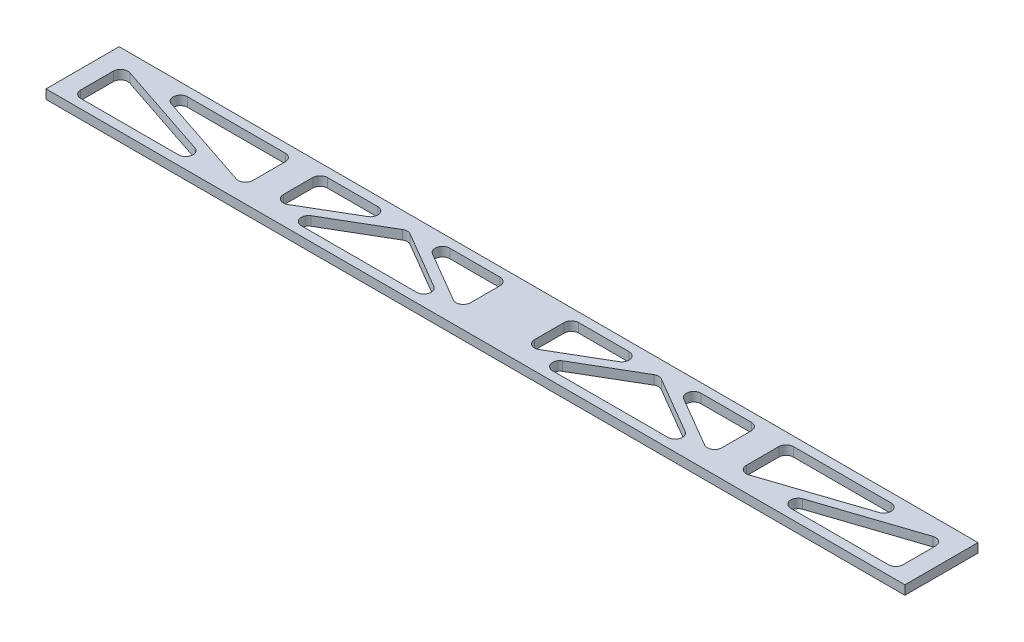
SolidWorks part; units mm, degrees
material "Plywood"
ref_plane "Front Plane" through (0, 0, 0) normal (0, 0, 1) x (1, 0, 0)
ref_plane "Top Plane" through (0, 0, 0) normal (0, 1, 0) x (1, 0, 0)
ref_plane "Right Plane" through (0, 0, 0) normal (1, 0, 0) x (0, 0, -1)
sketch "Sketch1" plane through (0, 0, 0) normal (0, 1, 0) x (1, 0, 0)
  line L1 (149.225, -12.7) -> (-149.225, -12.7)
  line L2 (149.225, -12.7) -> (149.225, 12.7)
  line L3 (149.225, 12.7) -> (-149.225, 12.7)
  line L4 (-149.225, -12.7) -> (-149.225, 12.7)
  point P0 (0, 12.7)
  point P6 (-149.225, 0)
  dimension "D1" = 25.4
  dimension "D2" = 298.45
extrude "Boss-Extrude1" add sketch "Sketch1" along normal blind 3.175
sketch "Sketch2" plane through (0, 3.175, 0) normal (0, 1, 0) x (1, 0, 0)
  line L0 (149.225, -12.7) -> (149.225, 12.7) construction
  line L2 (-149.225, 12.7) -> (-149.225, -12.7) construction
  line L4 (149.225, -12.7) -> (149.225, 12.7)
  line L6 (-149.225, 12.7) -> (-149.225, -12.7)
  line L8 (149.225, 9.525) -> (-149.225, 9.525)
  line L9 (-149.225, -9.525) -> (149.225, -9.525)
  line L10 (-142.875, 9.525) -> (-142.875, -9.525)
  line L11 (-80.9625, 9.525) -> (-80.9625, -9.525) construction
  line L12 (142.875, 9.525) -> (142.875, -9.525)
  line L13 (0, -9.525) -> (0, 9.525) construction
  line L14 (11.1125, 9.525) -> (11.1125, -9.525)
  line L15 (-11.1125, 9.525) -> (-11.1125, -9.525)
  line L16 (-85.725, 9.525) -> (-85.725, -9.525)
  line L17 (-76.2, 9.525) -> (-76.2, -9.525)
  line L18 (80.9625, 9.525) -> (80.9625, -9.525) construction
  line L19 (85.725, 9.525) -> (85.725, -9.525)
  line L20 (76.2, 9.525) -> (76.2, -9.525)
  line L21 (-76.2, -9.525) -> (-43.6562, 9.525)
  line L22 (-43.6562, 9.525) -> (-11.1125, -9.525)
  line L23 (-85.725, -9.525) -> (-142.875, 9.525)
  line L24 (11.1125, -9.525) -> (43.6562, 9.525)
  line L25 (43.6562, 9.525) -> (76.2, -9.525)
  line L26 (85.725, -9.525) -> (142.875, 9.525)
  line L27 (-85.223, -8.019) -> (-142.373, 11.031)
  line L28 (-75.398, -10.895) -> (-43.6562, 7.6855)
  line L29 (-43.6562, 7.6855) -> (-11.9145, -10.895)
  line L30 (11.9145, -10.895) -> (43.6562, 7.6855)
  line L31 (43.6562, 7.6855) -> (75.398, -10.895)
  line L32 (86.227, -11.031) -> (143.377, 8.019)
  line L33 (-86.227, -11.031) -> (-143.377, 8.019)
  line L34 (-77.002, -8.155) -> (-43.6562, 11.3645)
  line L35 (-43.6562, 11.3645) -> (-10.3105, -8.155)
  line L36 (10.3105, -8.155) -> (43.6562, 11.3645)
  line L37 (43.6562, 11.3645) -> (77.002, -8.155)
  line L38 (85.223, -8.019) -> (142.373, 11.031)
  dimension "D1" = 3.175
  dimension "D2" = 3.175
  dimension "D3" = 6.35
  dimension "D4" = 6.35
  dimension "D11" = 4.7625
  dimension "D12" = 4.7625
  dimension "D8" = 9.525
  dimension "D9" = 4.7625
  dimension "D7" = 63.5
  dimension "D10" = 63.5
  dimension "D5" = 22.225
  dimension "D6" = 11.1125
  dimension "D13" = 1.5875
  dimension "D14" = 1.5875
extrude "Cut-Extrude1" cut sketch "Sketch2" against normal through all contours L9 L33 L10 | L27 L16 L8 | L17 L34 L8 | L29 L28 L9 | L8 L35 L15 | L14 L36 L8 | L31 L30 L9 | L8 L37 L20 | L19 L38 L8 | L32 L9 L12 region at (125.4984, 3.175, 3.7328) region at (103.1016, 3.175, -3.7328) region at (66.3996, 3.175, -3.7882) region at (43.6562, 3.175, 3.7882) region at (20.9129, 3.175, -3.7882) region at (-20.9129, 3.175, -3.7882) region at (-43.6562, 3.175, 3.7882) region at (-66.3996, 3.175, -3.7882) region at (-103.1016, 3.175, -3.7328) region at (-125.4984, 3.175, 3.7328)
fillet "Fillet1" radius 2.54 30 edges at (-14.2549, 1.5875, 9.525) (-73.0576, 1.5875, 9.525) (-43.6562, 1.5875, -7.6855) (-11.1125, 1.5875, 7.6855) (-40.5138, 1.5875, -9.525) (-11.1125, 1.5875, -9.525) (-46.7987, 1.5875, -9.525) (-76.2, 1.5875, 7.6855) (-76.2, 1.5875, -9.525) (73.0576, 1.5875, 9.525) (14.2549, 1.5875, 9.525) (43.6562, 1.5875, -7.6855) (142.875, 1.5875, -7.8516) (142.875, 1.5875, 9.525) (90.7451, 1.5875, 9.525) (40.5138, 1.5875, -9.525) (11.1125, 1.5875, 7.6855) (11.1125, 1.5875, -9.525) (76.2, 1.5875, 7.6855) (46.7987, 1.5875, -9.525) (76.2, 1.5875, -9.525) (137.8549, 1.5875, -9.525) (85.725, 1.5875, 7.8516) (85.725, 1.5875, -9.525) (-137.8549, 1.5875, -9.525) (-85.725, 1.5875, 7.8516) (-85.725, 1.5875, -9.525) (-90.7451, 1.5875, 9.525) (-142.875, 1.5875, 9.525) (-142.875, 1.5875, -7.8516)
move or copy body "Body-Move/Copy1" [suppressed] bodies to move or copy 102 parameters "D1"=0, "D2"=0, "D3"=0
move or copy body "Body-Move/Copy2" [suppressed] bodies to move or copy 103 parameters "D1"=0, "D2"=0, "D3"=0
move or copy body "Body-Move/Copy3" [suppressed] bodies to move or copy 104 parameters "D1"=0, "D2"=0, "D3"=0
equation "\"D10@Sketch2\"=\"D7@Sketch2\""
equation "\"D6@Sketch2\"=\"D5@Sketch2\"/2"
